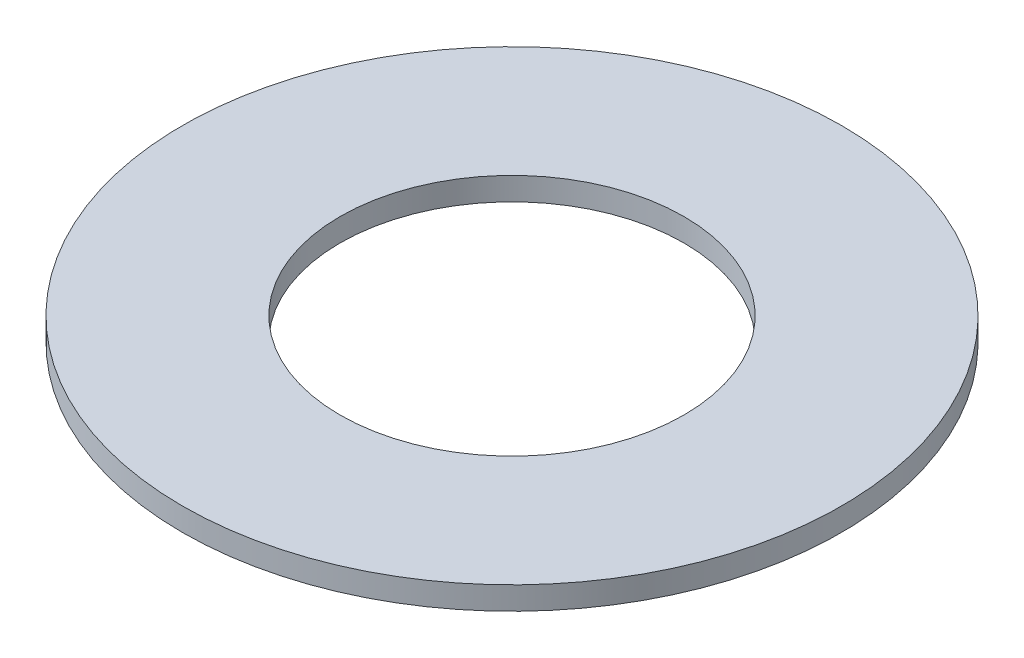
SolidWorks part; units mm, degrees
ref_plane "Front Plane" through (0, 0, 0) normal (0, 0, 1) x (1, 0, 0)
ref_plane "Top Plane" through (0, 0, 0) normal (0, 1, 0) x (1, 0, 0)
ref_plane "Right Plane" through (0, 0, 0) normal (1, 0, 0) x (0, 0, -1)
sketch "Sketch1" plane through (0, 0, 0) normal (0, 1, 0) x (1, 0, 0)
  circle A0 centre (0, 0) radius 57.5
  dimension "FLANGE_OD" = 115
extrude "Boss-Extrude1" add sketch "Sketch1" along normal blind 4
sketch "Sketch2" plane through (0, 0, 0) normal (0, 1, 0) x (1, 0, 0)
  circle A0 centre (0, 0) radius 30
  dimension "BORE_D" = 60
extrude "Cut-Extrude1" cut sketch "Sketch2" along normal through all
sketch "Sketch3" plane through (0, 4, 0) normal (0, 1, 0) x (1, 0, 0)
  circle A0 centre (0, 0) radius 19.8504 construction
  circle A1 centre (-19.8504, 0) radius 2.2863
  dimension "BOLT_D" = 4.5725
  dimension "BOLT_PCD" = 39.7008
extrude "Cut-Extrude2" cut sketch "Sketch3" against normal blind 3.0728 rebuild error yes
pattern_circular "CirPattern1" count 6 over 360 rebuild error yes
